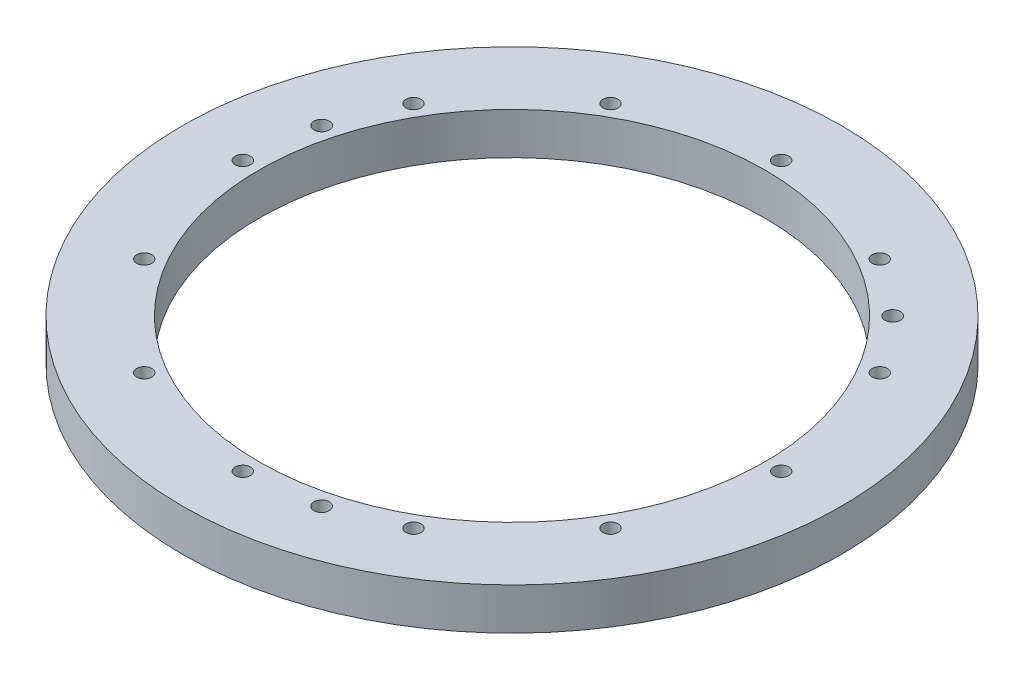
SolidWorks part; units mm, degrees
material "6061 Alloy"
ref_plane "Front Plane" through (0, 0, 0) normal (0, 0, 1) x (1, 0, 0)
ref_plane "Top Plane" through (0, 0, 0) normal (0, 1, 0) x (1, 0, 0)
ref_plane "Right Plane" through (0, 0, 0) normal (1, 0, 0) x (0, 0, -1)
sketch "Sketch1" plane through (0, 0, 0) normal (0, 1, 0) x (1, 0, 0)
  circle A0 centre (0, 0) radius 49.2125
  circle A1 centre (0, 0) radius 64.135
  circle A3 centre (0, -52.3875) radius 1.4732
  circle A4 centre (-26.1938, -45.3689) radius 1.4732
  circle A5 centre (-45.3689, -26.1937) radius 1.4732
  circle A6 centre (-52.3875, 0) radius 1.4732
  circle A7 centre (-45.3689, 26.1938) radius 1.4732
  circle A8 centre (-26.1937, 45.3689) radius 1.4732
  circle A9 centre (0, 52.3875) radius 1.4732
  circle A10 centre (26.1938, 45.3689) radius 1.4732
  circle A11 centre (45.3689, 26.1937) radius 1.4732
  circle A12 centre (52.3875, 0) radius 1.4732
  circle A13 centre (45.3689, -26.1938) radius 1.4732
  circle A14 centre (26.1937, -45.3689) radius 1.4732
  point P21 (0, 0)
  dimension "D1" = 98.425
  dimension "D4" = 2.9464
  dimension "D5" = 52.3875
  dimension "D2" = 14.9225
  dimension "D6" = 12
extrude "Boss-Extrude1" add sketch "Sketch1" along normal blind 8.128 contours A0 | A1 region at (-62.321, 0, 0)
sketch "Sketch2" plane through (0, 8.128, 0) normal (0, 1, 0) x (1, 0, 0)
  circle A0 centre (-45.3689, 26.1938) radius 1.4732 construction
  circle A1 centre (-52.3875, 0) radius 1.4732 construction
  circle A2 centre (-45.3689, 26.1938) radius 1.4732 construction
  circle A3 centre (-52.3875, 0) radius 1.4732 construction
  arc A4 (-52.3875, 0) -> (-45.3689, 26.1938) centre (0, 0) cw construction
  circle A5 centre (-50.6024, 13.5589) radius 1.5
  dimension "D1" = 3
extrude "Cut-Extrude1" cut sketch "Sketch2" against normal through all
pattern_circular "CirPattern1" count 3 over 360 about axis through (0, 8.128, 0) along (0, 1, 0) of "Cut-Extrude1"
equation "\"Middle Coupler Inner Daimeter\"= 3.875in"
equation "\"Middle Coupler  Wall Thickness\" = 0.25in"
equation "\"Middle Coupler Bottom Thickness\"= 0.2in"
equation "\"Bearing Rail Offset\"= 0.45in"
equation "\"3-56 UNF Tap\"= 0.089in"
equation "\"3-56 UNF Clearance\"= 0.104in"
equation "\"D5@Sketch1\"=(\"Middle Coupler Inner Daimeter\"*2+0.5)/4in"
equation "\"Ball Bearing Distance\"= 0.03in"
equation "\"D4@Sketch1\"=\"4-40 Clearance\""
equation "\"D1@Sketch1\"=\"Middle Coupler Inner Daimeter\""
equation "\"TCA Outer Diameter\" = 6in"
equation "\"Interstage Aeroframe Wall Thickness\" = 0.072in"
equation "\"Compression Spring OD\"= 0.42in"
equation "\"10-24 Tap\"= 0.1495in"
equation "\"10-24 Clearance\"= 0.196in"
equation "\"Lower Stage Fuselage Wall Thickness\" = 0.25in"
equation "\"6-32 Tap\" = 0.107in"
equation "\"1/4-20 Tap\" = 0.201in"
equation "\"D2@Sketch1\"=0.5875"
equation "\"D1@Sketch2\"=3mm"
equation "\"3-48 Tap\"= 0.079in"
equation "\"4-40 Tap\"= 0.089in"
equation "\"3-48 Clearance\" = 0.104in"
equation "\"4-40 Clearance\" = 0.116in"
equation "\"6-32 Clearance\" = 0.144in"
equation "\"12-24 Tap\" = 0.177in"
equation "\"12-24 Major Diameter\"= 0.216in"
